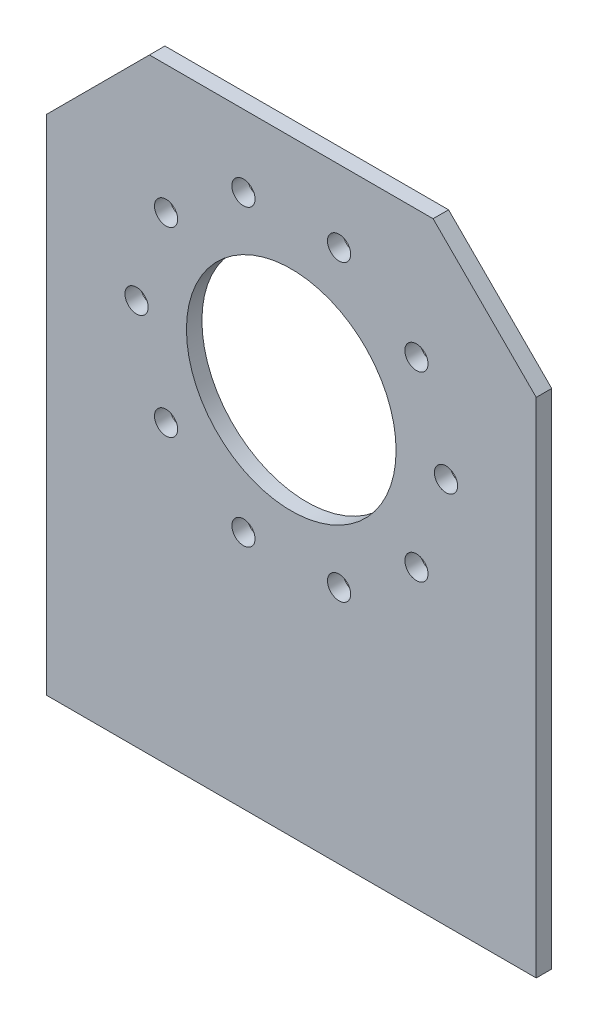
SolidWorks part; units mm, degrees
ref_plane "Front Plane" through (0, 0, 0) normal (0, 0, 1) x (1, 0, 0)
ref_plane "Top Plane" through (0, 0, 0) normal (0, 1, 0) x (1, 0, 0)
ref_plane "Right Plane" through (0, 0, 0) normal (1, 0, 0) x (0, 0, -1)
sketch "Sketch1" plane through (0, 0, 0) normal (0, 0, 1) x (1, 0, 0)
  line L0 (-95, 77.5) -> (-55, 117.5)
  line L1 (-95, -117.5) -> (95, -117.5)
  line L2 (-95, -117.5) -> (-95, 77.5)
  line L3 (-55, 117.5) -> (55, 117.5)
  line L4 (95, -117.5) -> (95, 77.5)
  line L5 (-95, -117.5) -> (95, 117.5) construction
  line L6 (-95, 117.5) -> (95, -117.5) construction
  line L7 (55, 117.5) -> (95, 77.5)
  circle A0 centre (0, 32.5) radius 40.65
  circle A31 centre (-60, 32.5) radius 4.5
  circle A32 centre (-48.541, 67.7671) radius 4.5
  circle A33 centre (-18.541, 89.5634) radius 4.5
  circle A34 centre (18.541, 89.5634) radius 4.5
  circle A35 centre (48.541, 67.7671) radius 4.5
  circle A36 centre (60, 32.5) radius 4.5
  circle A37 centre (48.541, -2.7671) radius 4.5
  circle A38 centre (18.541, -24.5634) radius 4.5
  circle A39 centre (-18.541, -24.5634) radius 4.5
  circle A40 centre (-48.541, -2.7671) radius 4.5
  point P0 (0, 0)
  point P14 (-19.103, 6.2069)
  point P18 (-19.103, 6.2069)
  point P19 (-30.9093, 22.4569)
  point P22 (-30.9093, 42.5431)
  point P23 (-30.9093, 22.4569)
  point P25 (-19.103, 58.7931)
  point P27 (-30.9093, 42.5431)
  point P28 (0, 65)
  point P31 (19.103, 58.7931)
  point P32 (-19.103, 58.7931)
  point P34 (30.9093, 42.5431)
  point P36 (0, 65)
  point P37 (30.9093, 22.4569)
  point P40 (19.103, 6.2069)
  point P41 (19.103, 58.7931)
  point P43 (0, 32.5)
  point P45 (30.9093, 42.5431)
  point P48 (30.9093, 22.4569)
  point P51 (19.103, 6.2069)
  point P54 (0, 32.5)
  dimension "D3" = 81.3
  dimension "D5" = 9
  dimension "D1" = 235
  dimension "D2" = 190
  dimension "D4" = 150
  dimension "D6" = 60
  dimension "D7" = 10
  dimension "D10" = 10
extrude "Boss-Extrude1" add sketch "Sketch1" along normal blind 6
